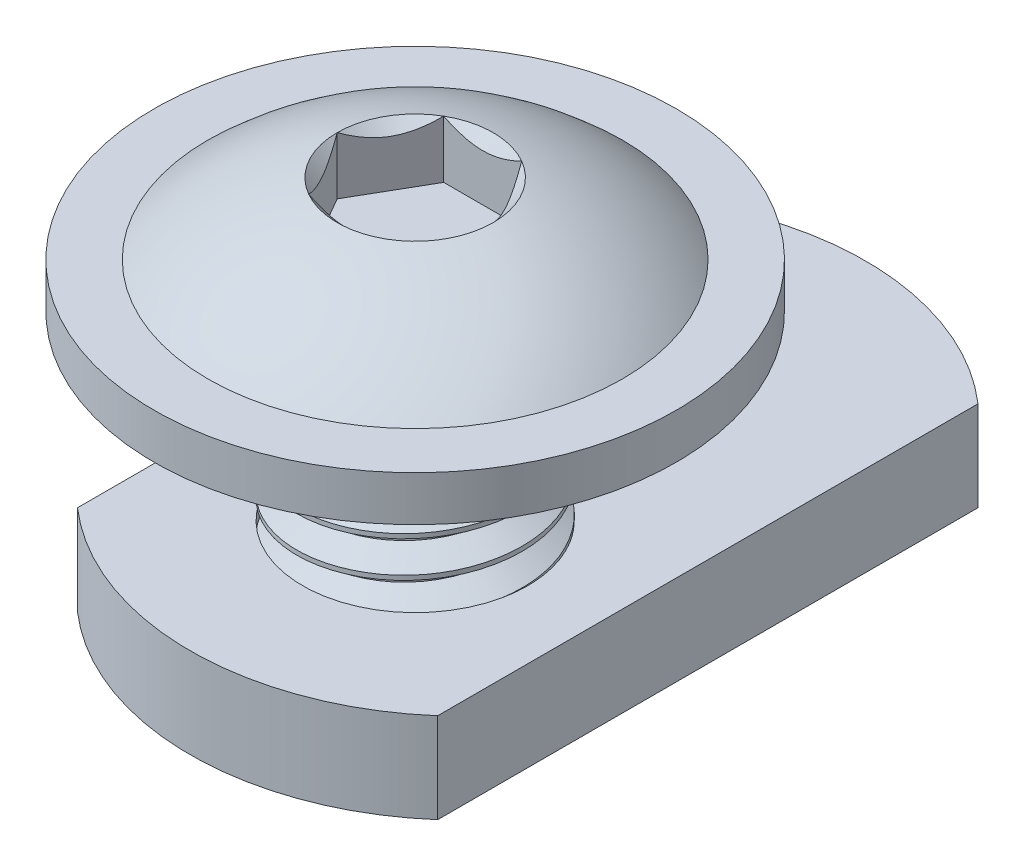
SolidWorks part; units mm, degrees
ref_plane "Front Plane" through (0, 0, 0) normal (0, 0, 1) x (1, 0, 0)
ref_plane "Top Plane" through (0, 0, 0) normal (0, 1, 0) x (1, 0, 0)
ref_plane "Right Plane" through (0, 0, 0) normal (1, 0, 0) x (0, 0, -1)
sketch "Sketch1" plane through (0, 0, 0) normal (0, 0, 1) x (1, 0, 0)
  line L0 (0, 0) -> (0, 10.8) construction
  line L1 (0, 0) -> (-2.5, 0)
  line L2 (-2.5, 0) -> (-2.5, 8)
  line L3 (-2.5, 8) -> (-4.6, 8)
  line L4 (-4.6, 8) -> (-4.6, 9)
  line L6 (0, 0) -> (0, 10.8)
  arc A0 (-4.6, 9) -> (0, 10.8) centre (0, 4.0222) cw
  dimension "screw od" = 5
  dimension "head od" = 9.2
  dimension "D4" = 1
  dimension "head height" = 2.8
  dimension "screw length" = 8
sketch "Sketch2" plane through (0, 0, 0) normal (0, 0, 1) x (1, 0, 0)
  line L0 (0, 0) -> (0, 10.8) construction
  line L1 (-2.5, 8) -> (-4.6, 8) construction
  line L2 (0, 0) -> (-2.5, 0) construction
  line L3 (-2.5, 0) -> (-2.5, 8) construction
  line L4 (0, 0) -> (0, 8)
  line L5 (0, 8) -> (-2.5, 8)
  line L6 (0, 0) -> (-2.5, 0)
  line L7 (-2.5, 0) -> (-2.5, 8)
revolve "Revolve2" add sketch "Sketch2" angle 360 about L0
sketch "Sketch3" plane through (0, 8, 0) normal (0, 1, 0) x (1, 0, 0)
  circle A1 centre (0, 0) radius 2.5
  circle A2 centre (0, 0) radius 2.5
  dimension "D1" = 0
curve "Helix/Spiral1" pitch 0.8 height 8.1875 turns 10.2344 parameters "pitch"=0.8
chamfer "Chamfer1" distance 0.8 angle 45 1 edges at (0, 0, -2.5)
sketch "Sketch4" plane through (0, 0, 0) normal (0, 0, 1) x (1, 0, 0)
  line L0 (2.5, 8.7) -> (2.5, 8)
  line L1 (2.5, 8) -> (1.9804, 8.3)
  line L2 (1.9804, 8.3) -> (1.9804, 8.4)
  line L3 (1.9804, 8.4) -> (2.5, 8.7)
  line L4 (1.9804, 8.35) -> (2.5, 8.35) construction
  line L5 (2.2402, 8.15) -> (2.2402, 8.55) construction
  line L7 (2.5, 8) -> (-2.5, 8) construction
  dimension "D1" = 60
  dimension "D2" = 0.1
  dimension "D3" = 0.4
sweep "Cut-Sweep1" cut profiles "Sketch4" path "Helix/Spiral1"
sketch "Sketch5" plane through (0, 0, 0) normal (0, 0, 1) x (1, 0, 0)
  line L0 (0, 0) -> (0, 10.8) construction
  line L1 (-2.5, 8) -> (-4.6, 8) construction
  line L3 (-4.6, 8) -> (-4.6, 9) construction
  line L4 (0, 8) -> (0, 10.8)
  line L5 (0, 8) -> (-4.6, 8)
  line L7 (-4.6, 8) -> (-4.6, 9)
  arc A0 (0, 10.8) -> (-4.6, 9) centre (0, 4.0222) ccw construction
  arc A1 (0, 10.8) -> (-4.6, 9) centre (0, 4.0222) ccw
revolve "Revolve3" add sketch "Sketch5" angle 360 about L0
sketch "Sketch20" plane through (0, 8, 0) normal (0, -1, 0) x (1, 0, 0)
  circle A0 centre (0, 0) radius 5.8
  dimension "D1" = 11.6
extrude "Boss-Extrude1" add sketch "Sketch20" against normal blind 1
ref_plane "Plane1" through (0, 10.8, 0) normal (0, 1, 0) x (-1, 0, 0)
sketch "Sketch6" plane through (0, 10.8, 0) normal (0, 1, 0) x (-1, 0, 0)
  line L1 (0.866, 1.5) -> (-0.866, 1.5)
  line L2 (-0.866, 1.5) -> (-1.7321, 0)
  line L3 (-1.7321, 0) -> (-0.866, -1.5)
  line L4 (-0.866, -1.5) -> (0.866, -1.5)
  line L5 (0.866, -1.5) -> (1.7321, 0)
  line L6 (1.7321, 0) -> (0.866, 1.5)
  circle A0 centre (0, 0) radius 1.5 construction
  dimension "hex" = 3
extrude "Cut-Extrude1" cut sketch "Sketch6" against normal blind 1.5
ref_plane "Plane2" through (0, 10.575, 0) normal (0, 1, 0) x (-1, 0, 0)
sketch "Sketch7" plane through (0, 10.575, 0) normal (0, 1, 0) x (-1, 0, 0)
  circle A0 centre (0, 0) radius 1.7321
extrude "Cut-Extrude2" cut sketch "Sketch7" against normal up to surface (1.275 mm away) draft 45 and the other way through all
ref_plane "Plane3" through (0, 2.475, 0) normal (0, -1, 0) x (1, 0, 0)
sketch "Sketch8" plane through (0, 2.475, 0) normal (0, -1, 0) x (1, 0, 0)
  line L0 (-4, -2.5) -> (4, -2.5) construction
  line L1 (0, -2.5) -> (0, 0) construction
  line L2 (-4, 3.5) -> (-4, -8.5)
  line L4 (4, 3.5) -> (4, -8.5)
  circle A0 centre (0, 0) radius 2.5
  arc A1 (-4, 3.5) -> (4, 3.5) centre (0, -1.0833) cw
  arc A2 (-4, -8.5) -> (4, -8.5) centre (0, -3.9167) ccw
  dimension "D1" = 12
  dimension "D4" = 5
  dimension "D3" = 15
  dimension "D2" = 8
extrude "Extrude1" add sketch "Sketch8" along normal mid plane 3 separate body
sketch "Sketch9" plane through (0, 0.975, 0) normal (0, -1, 0) x (1, 0, 0)
  line L2 (4, -8.5) -> (4, 3.5)
  line L3 (-4, 3.5) -> (-4, -8.5)
  line L4 (4, -8.5) -> (4, 3.5)
  line L5 (-4, 3.5) -> (-4, -8.5)
  circle A0 centre (0, 0) radius 3
  arc A2 (-4, -8.5) -> (4, -8.5) centre (0, -3.9167) ccw
  arc A3 (4, 3.5) -> (-4, 3.5) centre (0, -1.0833) ccw
  arc A4 (-4, -8.5) -> (4, -8.5) centre (0, -3.9167) ccw
  arc A5 (4, 3.5) -> (-4, 3.5) centre (0, -1.0833) ccw
  dimension "D2" = 6
  dimension "D1" = 0
extrude "Cut-Extrude3" cut sketch "Sketch9" against normal offset from surface (1 mm away) 2 up to face at (0, 3.975, -2.5)
sketch "Sketch10" [suppressed] plane through (0, 6.475, 0) normal (0, -1, 0) x (1, 0, 0)
  line L0 (-9, -11.9) -> (-9, 12.9)
  line L1 (9, 12.9) -> (9, -11.9)
  line L2 (-19.9844, 16) -> (0, 16) construction
  circle A0 centre (0, 0) radius 4
  arc A1 (9, 12.9) -> (-9, 12.9) centre (0, 1.3855) ccw
  arc A2 (-9, -11.9) -> (9, -11.9) centre (0, -0.3855) ccw
  dimension "D2" = 5
  dimension "D3" = 8
  dimension "D4" = 1.5
  dimension "D5" = 5
  dimension "D1" = 15
extrude "Extrude2" [suppressed] add sketch "Sketch10" along normal mid plane 3 separate body
sketch "Sketch11" [suppressed] plane through (0, 3.725, 0) normal (0, -1, 0) x (1, 0, 0)
  line L2 (9, -11.9) -> (9, 12.9)
  line L3 (-9, 12.9) -> (-9, -11.9)
  line L4 (9, -11.9) -> (9, 12.9)
  line L5 (-9, 12.9) -> (-9, -11.9)
  circle A0 centre (0, 0) radius 2.75 construction
  circle A3 centre (0, 0) radius 4.5
  arc A5 (-9, -11.9) -> (9, -11.9) centre (0, -0.3855) ccw
  arc A6 (9, 12.9) -> (-9, 12.9) centre (0, 1.3855) ccw
  arc A7 (-9, -11.9) -> (9, -11.9) centre (0, -0.3855) ccw
  arc A8 (9, 12.9) -> (-9, 12.9) centre (0, 1.3855) ccw
  dimension "D1" = 6
  dimension "D2" = 0
extrude "Cut-Extrude4" [suppressed] cut sketch "Sketch11" against normal offset from surface (1.5 mm away) 2
sketch "Sketch12" [suppressed] plane through (0, 0, 0) normal (0, 0, 1) x (1, 0, 0)
  line L0 (-6.8072, 17.78) -> (-5.4458, 17.78) construction
  line L1 (-6.8072, 17.78) -> (-5.4458, 17.78)
  line L2 (9.2481, 20.0393) -> (-9.2481, 20.0393) construction
  line L3 (0, 0) -> (0, 53.1234) construction
  line L4 (-3.9688, 15.875) -> (-6.8072, 15.875) construction
  line L5 (-9.398, 15.875) -> (-3.9688, 15.875)
  line L6 (-9.398, 15.875) -> (-9.398, 14.605)
  line L7 (-9.398, 14.605) -> (-3.9688, 14.605)
  line L8 (-3.9688, 15.875) -> (-3.9688, 14.605)
  arc A0 (0, 20.6375) -> (-5.4458, 17.78) centre (0, 14.0195) ccw construction
  arc A1 (-2.7496, 20.0393) -> (-5.4458, 17.78) centre (0, 14.0195) ccw
  arc A2 (-6.8072, 17.78) -> (-2.7496, 20.0393) centre (0, 10.3277) cw
  dimension "D1" = 9.398
  dimension "D2" = 1.27
revolve "Revolve4" [suppressed] add sketch "Sketch12" angle 360 about L0
sketch "Sketch13" [suppressed] plane through (0, 6.35, 0) normal (0, -1, 0) x (1, 0, 0)
  line L0 (-7.9375, 4.7562) -> (-7.9375, -17.4688)
  line L1 (7.9375, 4.7562) -> (7.9375, -17.4688)
  circle A0 centre (0, 0) radius 3.9688
  arc A1 (-7.9375, 4.7562) -> (7.9375, 4.7562) centre (0, -3.5782) cw
  arc A2 (-7.9375, -17.4688) -> (7.9375, -17.4688) centre (0, -9.1345) ccw
  dimension "D2" = 28.575
  dimension "D3" = 3.9624
  dimension "D4" = 7.9375
  dimension "D1" = 15.875
  dimension "D5" = 3.175
extrude "Extrude4" [suppressed] add sketch "Sketch13" along normal mid plane 5.8928 separate body
sketch "Sketch14" [suppressed] plane through (0, 3.4036, 0) normal (0, -1, 0) x (1, 0, 0)
  line L2 (-7.9375, 4.7561) -> (-7.9375, -17.4688)
  line L3 (7.9375, -17.4688) -> (7.9375, 4.7562)
  line L4 (-7.9375, 4.7561) -> (-7.9375, -17.4688)
  line L5 (7.9375, -17.4688) -> (7.9375, 4.7562)
  arc A2 (7.9375, 4.7562) -> (-7.9375, 4.7561) centre (0, -3.5782) ccw
  arc A3 (-7.9375, -17.4688) -> (7.9375, -17.4688) centre (0, -9.1345) ccw
  arc A4 (7.9375, 4.7562) -> (-7.9375, 4.7561) centre (0, -3.5782) ccw
  arc A5 (-7.9375, -17.4688) -> (7.9375, -17.4688) centre (0, -9.1345) ccw
  circle A6 centre (0, 0) radius 5.4927
  circle A7 centre (0, 0) radius 5.4927
  dimension "D1" = 0
  dimension "D2" = 1.524
extrude "Cut-Extrude7" [suppressed] cut sketch "Sketch14" against normal offset from surface (1.8034 mm away) 4.0894
sketch "Sketch15" [suppressed] plane through (0, 0, 0) normal (0, 0, 1) x (1, 0, 0)
  line L0 (-6.6675, 19.6774) -> (-6.9, 17.3714) construction
  line L1 (-6.6675, 19.6774) -> (-6.9, 17.3714)
  line L2 (7.59, 20.3045) -> (-7.59, 20.3045) construction
  line L3 (0, 0) -> (0, 53.1234) construction
  arc A0 (0, 20.8) -> (-6.9, 17.3714) centre (0, 12.1426) ccw construction
  arc A1 (-2.8868, 20.3045) -> (-6.9, 17.3714) centre (0, 12.1426) ccw
  arc A2 (-2.8868, 20.3045) -> (-6.6675, 19.6774) centre (0, -8.8073) ccw
revolve "Revolve5" [suppressed] add sketch "Sketch15" angle 360 about L0
sketch "Sketch16" [suppressed] plane through (0, 3.175, 0) normal (0, -1, 0) x (1, 0, 0)
  line L0 (-6.3881, 8.443) -> (-6.3881, -33.843)
  line L1 (6.3881, 8.443) -> (6.3881, -33.843)
  line L2 (0, -25.4) -> (0, 0) construction
  line L3 (0, -12.7) -> (-6.3881, -12.7) construction
  line L4 (-6.3881, -27.1355) -> (-6.3881, 1.7355) construction
  circle A0 centre (0, 0) radius 3.175
  circle A1 centre (0, -25.4) radius 3.175
  arc A2 (-6.3881, 8.443) -> (6.3881, 8.443) centre (0, 1.7355) cw
  arc A3 (-6.3881, -33.843) -> (6.3881, -33.843) centre (0, -27.1355) ccw
  dimension "D1" = 25.4
  dimension "D2" = 6.35
  dimension "D4" = 47.3964
  dimension "D3" = 12.7762
  dimension "D5" = 2.5552
extrude "Extrude5" [suppressed] add sketch "Sketch16" along normal mid plane 4.0894 separate body
sketch "Sketch17" [suppressed] plane through (0, 1.1303, 0) normal (0, -1, 0) x (1, 0, 0)
  line L2 (-6.3881, 8.443) -> (-6.3881, -33.843)
  line L3 (6.3881, -33.843) -> (6.3881, 8.443)
  line L4 (-6.3881, 8.443) -> (-6.3881, -33.843)
  line L5 (6.3881, -33.843) -> (6.3881, 8.443)
  arc A2 (6.3881, 8.443) -> (-6.3881, 8.443) centre (0, 1.7355) ccw
  arc A3 (-6.3881, -33.843) -> (6.3881, -33.843) centre (0, -27.1355) ccw
  arc A4 (6.3881, 8.443) -> (-6.3881, 8.443) centre (0, 1.7355) ccw
  arc A5 (-6.3881, -33.843) -> (6.3881, -33.843) centre (0, -27.1355) ccw
  circle A6 centre (0, -25.4) radius 4.699
  circle A7 centre (0, -25.4) radius 4.699
  circle A10 centre (0, 0) radius 4.699
  circle A11 centre (0, 0) radius 4.699
  dimension "D1" = 0
  dimension "D2" = 1.524
  dimension "D3" = 1.524
pattern_linear "LPattern1" [suppressed] count 2 spacing 25.4
extrude "Cut-Extrude9" [suppressed] cut sketch "Sketch17" against normal offset from surface (1.4224 mm away) 2.667
sketch "Sketch18" [suppressed] plane through (0, 7.9375, 0) normal (0, -1, 0) x (1, 0, 0)
  line L0 (-7.9375, 13.462) -> (-7.9375, -51.562)
  line L1 (7.9375, 13.462) -> (7.9375, -51.562)
  line L2 (0, 0) -> (0, -38.1) construction
  line L3 (0, -19.05) -> (-7.9375, -19.05) construction
  line L4 (0, -19.05) -> (7.9375, -19.05) construction
  circle A0 centre (0, 0) radius 3.9688
  circle A1 centre (0, -38.1) radius 3.9688
  arc A2 (-7.9375, 13.462) -> (7.9375, 13.462) centre (0, 5.1276) cw
  arc A3 (-7.9375, -51.562) -> (7.9375, -51.562) centre (0, -43.2276) ccw
  dimension "D1" = 38.1
  dimension "D2" = 7.9375
  dimension "D4" = 3.175
  dimension "D5" = 71.374
  dimension "D3" = 15.875
extrude "Extrude6" [suppressed] add sketch "Sketch18" along normal mid plane 5.9944 separate body
sketch "Sketch19" [suppressed] plane through (0, 4.9403, 0) normal (0, -1, 0) x (1, 0, 0)
  line L2 (-7.9375, 13.462) -> (-7.9375, -51.562)
  line L3 (7.9375, -51.562) -> (7.9375, 13.462)
  line L4 (-7.9375, 13.462) -> (-7.9375, -51.562)
  line L5 (7.9375, -51.562) -> (7.9375, 13.462)
  arc A2 (7.9375, 13.462) -> (-7.9375, 13.462) centre (0, 5.1276) ccw
  arc A3 (-7.9375, -51.562) -> (7.9375, -51.562) centre (0, -43.2276) ccw
  arc A4 (7.9375, 13.462) -> (-7.9375, 13.462) centre (0, 5.1276) ccw
  arc A5 (-7.9375, -51.562) -> (7.9375, -51.562) centre (0, -43.2276) ccw
  circle A6 centre (0, 0) radius 5.4927
  circle A7 centre (0, 0) radius 5.4927
  circle A9 centre (0, -38.1) radius 5.4928
  circle A10 centre (0, -38.1) radius 5.4928
  dimension "D1" = 0
  dimension "D2" = 1.524
  dimension "D3" = 1.524
extrude "Cut-Extrude10" [suppressed] cut sketch "Sketch19" against normal offset from surface (2.1844 mm away) 3.81
pattern_linear "LPattern2" [suppressed] count 2 spacing 38.1
equation "\"D2@Sketch4\" = \"pitch@Helix/Spiral1\"*.125"
equation "\"D3@Sketch4\" = \"pitch@Helix/Spiral1\"*.5"
equation "\"D3@Helix/Spiral1\" = \"screw length@Sketch1\"+.18750"
equation "\"D1@Chamfer1\" = \"pitch@Helix/Spiral1\""
equation "\"D1@Cut-Extrude1\" = \"hex@Sketch6\"/2"
equation "\"D5@Sketch10\" = \"screw od@Sketch1\""
equation "\"D4@Sketch10\" = \"D1@Sketch10\"*.10"
equation "\"D5@Sketch13\" = \"D1@Sketch13\"*.2"
equation "\"D5@Sketch16\" = \"D3@Sketch16\"*.2"
equation "\"D4@Sketch18\" = \"D3@Sketch18\"*.2"
equation "\"D1@Sketch8\" = \"D3@Sketch8\"*.8"
